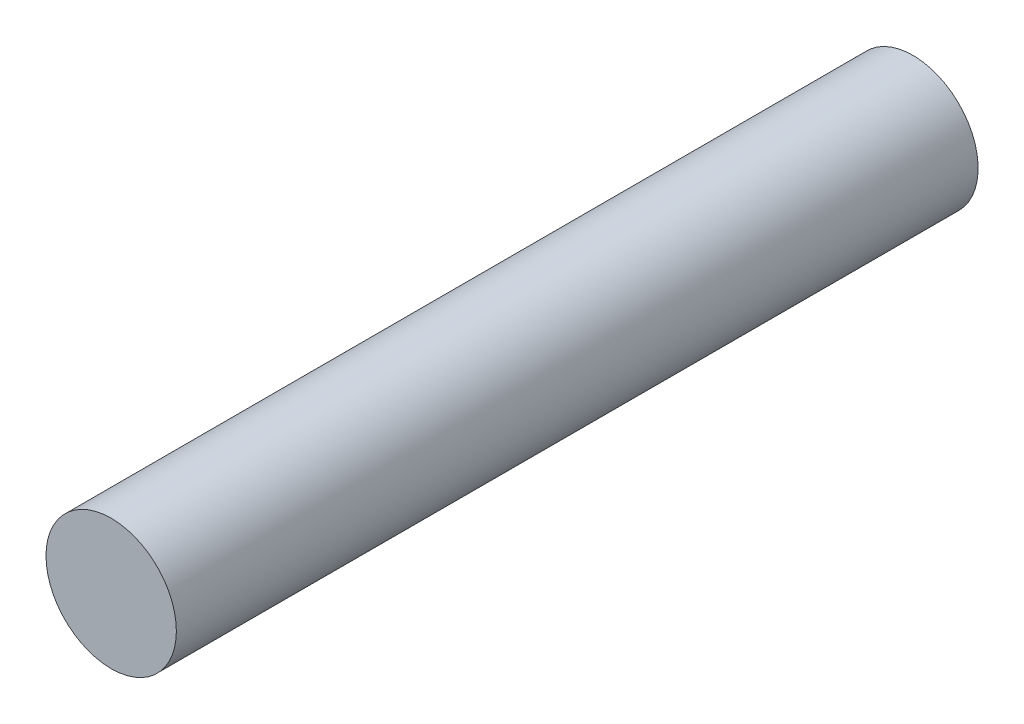
SolidWorks part; units mm, degrees
ref_plane "Front Plane" through (0, 0, 0) normal (0, 0, 1) x (1, 0, 0)
ref_plane "Top Plane" through (0, 0, 0) normal (0, 1, 0) x (1, 0, 0)
ref_plane "Right Plane" through (0, 0, 0) normal (1, 0, 0) x (0, 0, -1)
sketch "Sketch1" plane through (0, 0, 0) normal (0, 0, 1) x (1, 0, 0)
  line L0 (-4, 0) -> (4, 0) construction
  line L5 (0, 4) -> (0, -4) construction
  circle A1 centre (0, 0) radius 4
  point P7 (-4, 0)
  point P8 (4, 0)
  point P12 (0, -4)
  point P13 (0, 4)
  dimension "Diameter" = 8
sketch "Sketch2" plane through (0, 0, 0) normal (1, 0, 0) x (0, 0, -1)
  line L0 (-42, -4) -> (-42, 4) construction
  line L1 (50, -4) -> (-50, -4)
  line L2 (50, -4) -> (50, 4)
  line L3 (50, 4) -> (-50, 4)
  line L4 (-50, -4) -> (-50, 4)
  line L5 (50, -4) -> (-50, 4) construction
  line L6 (50, 4) -> (-50, -4) construction
  line L7 (42, -4) -> (42, 4) construction
  line L8 (-50, 3.44) -> (-49.44, 4) construction
  point P0 (0, 0)
  point P8 (-50, 4)
  point P9 (50, 4)
  point P14 (-42, 4)
  point P15 (-42, -4)
  point P16 (42, 4)
  point P17 (42, -4)
  point P25 (0, -4)
  dimension "Length" = 100
  dimension "D1" = 8
  dimension "D2" = 8
  dimension "Chamfer Typ," = 45
  dimension "D4" = 0.56
sketch "Sketch3" plane through (0, 0, 0) normal (0, 0, 1) x (1, 0, 0)
  circle A0 centre (0, 0) radius 4 construction
  circle A1 centre (0, 0) radius 4
extrude "Boss-Extrude1" add sketch "Sketch3" along normal up to vertex (50 mm away) and the other way up to vertex (50 mm away) up to point (0, 4, 50) other way up to point (0, 4, -50)
chamfer "Chamfer1" distance 0.56 angle 45 2 edges at (4, 0, -50) (4, 0, 50)
sketch "Sketch4" plane through (0, 0, 50) normal (0, 0, 1) x (1, 0, 0)
  circle A0 centre (0, 0) radius 8.463
extrude "Cut-Extrude1" cut sketch "Sketch4" against normal blind 25.4
sketch "Sketch5" plane through (0, 0, -50) normal (0, 0, -1) x (-1, 0, 0)
  circle A0 centre (0, 0) radius 6.6298
extrude "Cut-Extrude2" cut sketch "Sketch5" against normal blind 25.4
equation "\"D1@Sketch2\"=\"Diameter@Sketch1\""
equation "\"D2@Sketch2\"=\"Diameter@Sketch1\""
equation "\"D1@Chamfer1\"=\"Diameter@Sketch1\"*.07"
equation "\"D4@Sketch2\"=\"Diameter@Sketch1\"*.07"
equation "\"D2@Chamfer1\"=\"Chamfer Typ,@Sketch2\""
